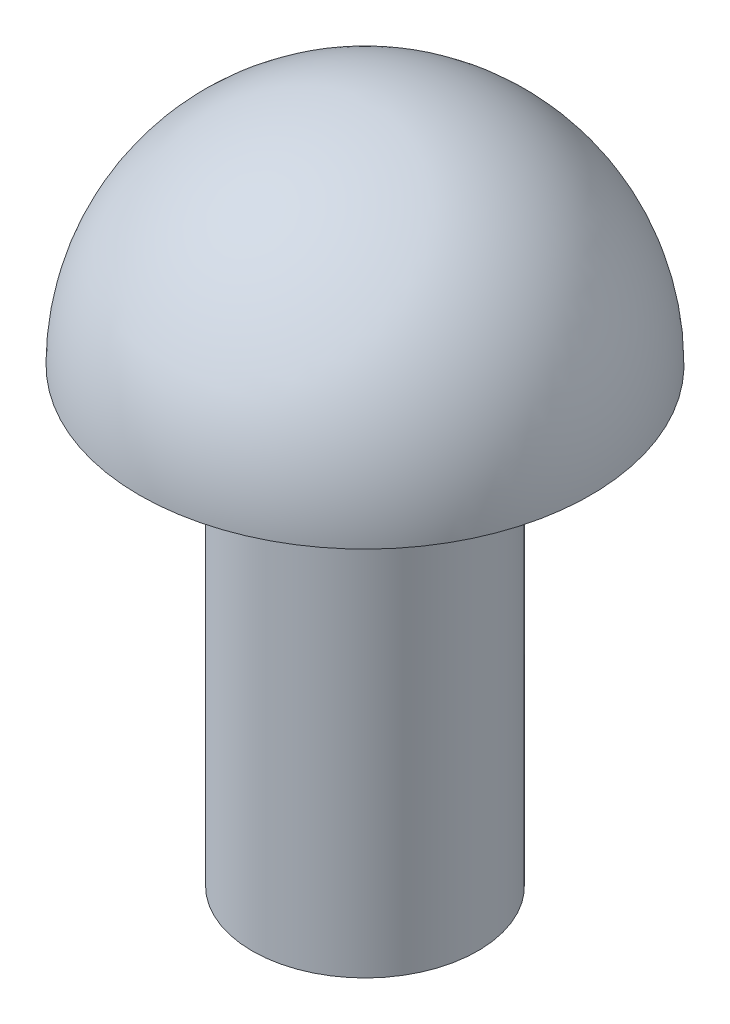
SolidWorks part; units mm, degrees
ref_plane "Front Plane" through (0, 0, 0) normal (0, 0, 1) x (1, 0, 0)
ref_plane "Top Plane" through (0, 0, 0) normal (0, 1, 0) x (1, 0, 0)
ref_plane "Right Plane" through (0, 0, 0) normal (1, 0, 0) x (0, 0, -1)
sketch "Sketch1" plane through (0, 0, 0) normal (0, 1, 0) x (1, 0, 0)
  circle A0 centre (0, 0) radius 2.5
  dimension "D1" = 5
extrude "Boss-Extrude1" add sketch "Sketch1" against normal blind 10 contours A0
sketch "Sketch2" plane through (0, 0, 0) normal (0, 1, 0) x (1, 0, 0)
  circle A0 centre (0, 0) radius 5
extrude "Boss-Extrude2" add sketch "Sketch2" along normal blind 5
fillet "Fillet1" radius 5 1 edges at (0, 5, 5)
